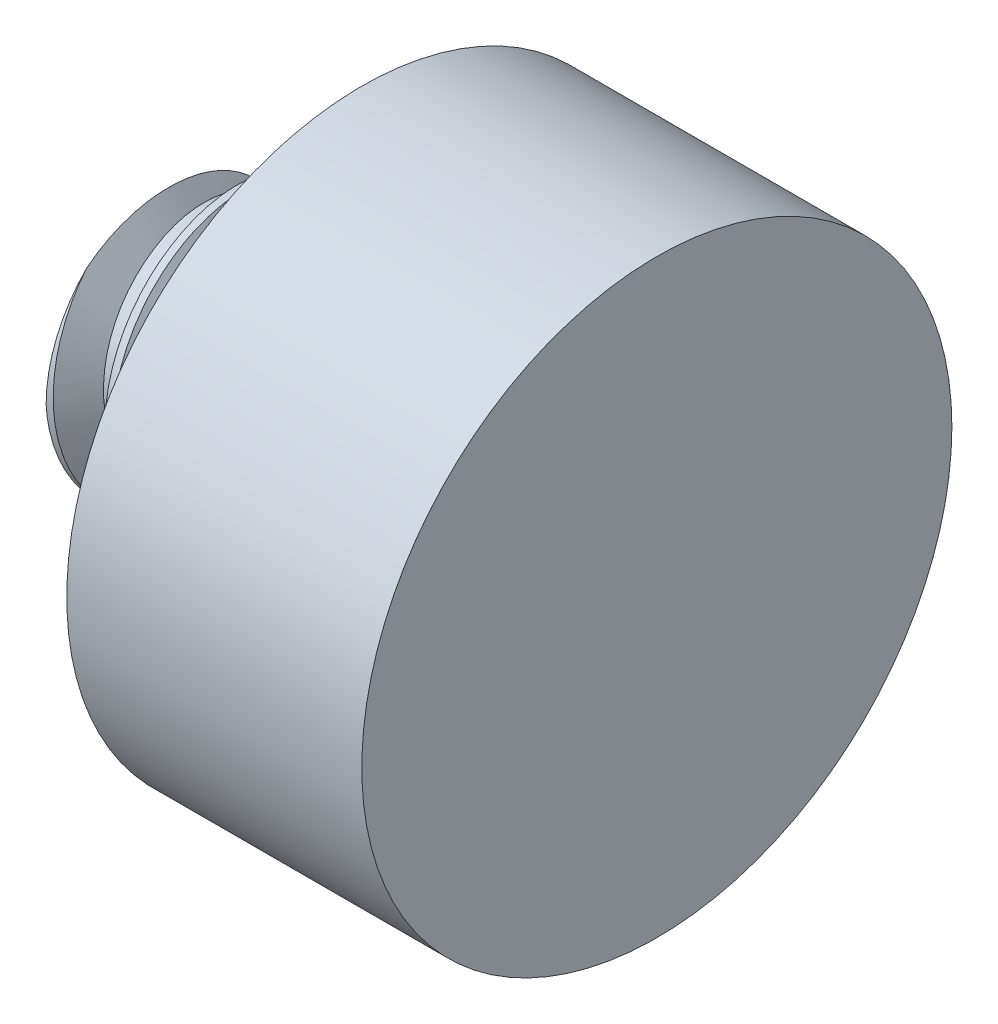
SolidWorks part; units mm, degrees
ref_plane "Front Plane" through (0, 0, 0) normal (0, 0, 1) x (1, 0, 0)
ref_plane "Top Plane" through (0, 0, 0) normal (0, 1, 0) x (1, 0, 0)
ref_plane "Right Plane" through (0, 0, 0) normal (1, 0, 0) x (0, 0, -1)
sketch "Sketch1" plane through (0, 0, 0) normal (0, 0, 1) x (1, 0, 0)
  line L0 (0, 0) -> (0, 2.9845)
  line L1 (0, 2.9845) -> (3.81, 2.9845)
  line L2 (3.81, 2.9845) -> (3.81, 6.35)
  line L3 (3.81, 6.35) -> (10.16, 6.35)
  line L4 (10.16, 6.35) -> (10.16, 0)
  line L5 (55, 0) -> (-55, 0) construction
  line L6 (10.16, 0) -> (0, 0)
  dimension "D1" = 2.9845
  dimension "D2" = 6.35
  dimension "D3" = 6.35
  dimension "D4" = 3.81
revolve "Revolve1" add sketch "Sketch1" angle 360 about L6
thread "Thread1" pitch 1.27 method cut profile "Thread Profile1" start angle 0, offset 0, length 3.81, pitch 1.27, diameter 5.969
ref_plane "Plane1" through (3.81, 0, 2.9845) normal (0, -1, 0) x (0, 0, 1)
sketch "Thread Profile1" plane through (3.81, 0, 2.9845) normal (0, -1, 0) x (0, 0, 1)
  line L0 (0, 0) -> (0, 1.27) construction
  line L11 (0, 0) -> (0, 1.1112)
  line L12 (0, 1.1112) -> (-0.6874, 0.7144)
  line L13 (-0.6874, 0.7144) -> (-0.6874, 0.3969)
  line L15 (-0.6874, 0.3969) -> (0, 0)
  line L17 (-0.6874, 0.5556) -> (0, 0.5556) construction
  point P2 (0, 0)
  dimension "Pitch" = 1.27
  dimension "Profile_Angle" = 60
  dimension "Profile_Land" = 0.3175
  dimension "Profile_Height" = 0.6874
